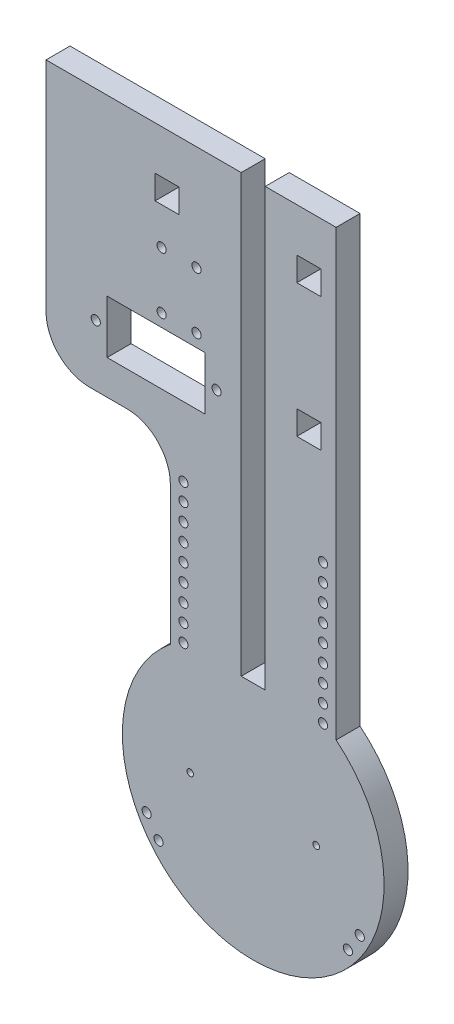
SolidWorks part; units mm, degrees
material "ﾁｰｸ材"
ref_plane "正面" through (0, 0, 0) normal (0, 0, 1) x (1, 0, 0)
ref_plane "平面" through (0, 0, 0) normal (0, 1, 0) x (1, 0, 0)
ref_plane "右側面" through (0, 0, 0) normal (1, 0, 0) x (0, 0, -1)
sketch "ｽｹｯﾁ1" plane through (0, 0, 0) normal (0, 0, 1) x (1, 0, 0)
  line L0 (19, 125) -> (-47.5, 125)
  line L2 (19, 125) -> (19, 23.2164)
  line L7 (-47.5, 65) -> (-47.5, 125)
  line L11 (-19, 65) -> (-19, 23.2164)
  line L12 (-19, 65) -> (-47.5, 65)
  arc A0 (-19, 23.2164) -> (19, 23.2164) centre (0, 0) ccw
  point P1 (-19, 85)
  dimension "D1" = 60
  dimension "D2" = 125
  dimension "D3" = 19
  dimension "D4" = 60
  dimension "D5" = 47.5
extrude "ﾎﾞｽ - 押し出し1" add sketch "ｽｹｯﾁ1" along normal blind 5.5
sketch "ｽｹｯﾁ3" plane through (0, 0, 5.5) normal (0, 0, 1) x (1, 0, 0)
  line L0 (0, 0) -> (0, 22.4882) construction
sketch "ｽｹｯﾁ5" plane through (0, 0, 5.5) normal (0, 0, 1) x (1, 0, 0)
  circle A0 centre (14.45, 0) radius 0.75
  circle A1 centre (-14.45, 0) radius 0.75
  dimension "D1" = 14.45
  dimension "D2" = 1.5
  dimension "D3" = 14.45
extrude "ｶｯﾄ - 押し出し3" cut sketch "ｽｹｯﾁ5" against normal through all
sketch "ｽｹｯﾁ6" plane through (0, 0, 5.5) normal (0, 0, 1) x (1, 0, 0)
  line L0 (0, 0) -> (-25.1601, -16.3392) construction
  line L1 (0, 0) -> (0, 22.4882) construction
  line L2 (-21.7018, -17.0742) -> (-24.425, -12.8809) construction
  line L3 (0, 0) -> (0, -5.9449) construction
  arc A0 (-19, 23.2164) -> (19, 23.2164) centre (0, 0) ccw construction
  circle A1 centre (-24.425, -12.8809) radius 1.05
  circle A2 centre (-21.7018, -17.0742) radius 1.05
  circle A3 centre (24.425, -12.8809) radius 1.05
  circle A4 centre (21.7018, -17.0742) radius 1.05
  point P12 (-23.0634, -14.9776)
  dimension "D2" = 5
  dimension "D3" = 2.1
  dimension "D4" = 2.1
  dimension "D1" = 123
  dimension "D5" = 27.5
extrude "ｶｯﾄ - 押し出し4" cut sketch "ｽｹｯﾁ6" against normal through all
sketch "ｽｹｯﾁ8" plane through (0, 0, 5.5) normal (0, 0, 1) x (1, 0, 0)
  line L0 (0, 0) -> (0, 22.4882) construction
  line L1 (15.5, 109.5) -> (10, 109.5)
  line L2 (15.5, 109.5) -> (15.5, 115)
  line L3 (15.5, 115) -> (10, 115)
  line L4 (10, 109.5) -> (10, 115)
  line L5 (-22.5, 115) -> (-17, 115)
  line L6 (-22.5, 115) -> (-22.5, 109.5)
  line L7 (-22.5, 109.5) -> (-17, 109.5)
  line L8 (-17, 115) -> (-17, 109.5)
  line L9 (19, 125) -> (-47.5, 125) construction
  line L10 (15.5, 79) -> (10, 79)
  line L11 (15.5, 79) -> (15.5, 84.5)
  line L12 (15.5, 84.5) -> (10, 84.5)
  line L13 (10, 79) -> (10, 84.5)
  point P10 (-17, 112.25)
  dimension "D1" = 5.5
  dimension "D2" = 10
  dimension "D3" = 17
  dimension "D4" = 10
  dimension "D5" = 25
extrude "ｶｯﾄ - 押し出し6" cut sketch "ｽｹｯﾁ8" against normal through all
sketch "ｽｹｯﾁ9" plane through (0, 0, 5.5) normal (0, 0, 1) x (1, 0, 0)
  line L0 (0, 0) -> (0, 22.4882) construction
  line L1 (0, 0) -> (0, 13.9203) construction
  circle A0 centre (16, 25) radius 1.05
  circle A1 centre (16, 29) radius 1.05
  circle A2 centre (16, 33) radius 1.05
  circle A3 centre (16, 37) radius 1.05
  circle A4 centre (16, 41) radius 1.05
  circle A5 centre (16, 45) radius 1.05
  circle A6 centre (16, 49) radius 1.05
  circle A7 centre (16, 53) radius 1.05
  circle A8 centre (16, 57) radius 1.05
  circle A9 centre (-16, 57) radius 1.05
  circle A10 centre (-16, 53) radius 1.05
  circle A11 centre (-16, 49) radius 1.05
  circle A12 centre (-16, 45) radius 1.05
  circle A13 centre (-16, 41) radius 1.05
  circle A14 centre (-16, 37) radius 1.05
  circle A15 centre (-16, 33) radius 1.05
  circle A16 centre (-16, 29) radius 1.05
  circle A17 centre (-16, 25) radius 1.05
  dimension "D1" = 2.1
  dimension "D2" = 16
  dimension "D4" = 25
  dimension "D3" = 9
extrude "ｶｯﾄ - 押し出し7" cut sketch "ｽｹｯﾁ9" against normal through all
sketch "ｽｹｯﾁ10" plane through (0, 0, 5.5) normal (0, 0, 1) x (1, 0, 0)
  line L0 (19, 125) -> (-47.5, 125) construction
  line L1 (2.75, 25) -> (-2.75, 25)
  line L2 (2.75, 25) -> (2.75, 125)
  line L3 (2.75, 125) -> (-2.75, 125)
  line L4 (-2.75, 25) -> (-2.75, 125)
  line L5 (2.75, 25) -> (-2.75, 125) construction
  line L6 (2.75, 125) -> (-2.75, 25) construction
  point P0 (0, 75)
  dimension "D1" = 5.5
  dimension "D2" = 25
extrude "ｶｯﾄ - 押し出し8" cut sketch "ｽｹｯﾁ10" against normal through all
sketch "ｽｹｯﾁ11" plane through (0, 0, 5.5) normal (0, 0, 1) x (1, 0, 0)
  line L0 (-2.75, 125) -> (-47.5, 125) construction
  line L1 (0, 0) -> (0, 22.4882) construction
  circle A0 centre (-13, 101) radius 1.05
  circle A1 centre (-21, 101) radius 1.05
  circle A2 centre (-13, 88) radius 1.05
  circle A3 centre (-21, 88) radius 1.05
  point P8 (-20.2729, 103.7087)
  dimension "D1" = 2.1
  dimension "D2" = 24
  dimension "D3" = 8
  dimension "D4" = 13
  dimension "D5" = 13
extrude "ｶｯﾄ - 押し出し9" cut sketch "ｽｹｯﾁ11" against normal through all
sketch "ｽｹｯﾁ12" plane through (0, 0, 5.5) normal (0, 0, 1) x (1, 0, 0)
  line L1 (-11, 72.9) -> (-33.5, 72.9)
  line L2 (-11, 72.9) -> (-11, 85.1)
  line L3 (-11, 85.1) -> (-33.5, 85.1)
  line L4 (-33.5, 72.9) -> (-33.5, 85.1)
  line L5 (-11, 72.9) -> (-33.5, 85.1) construction
  line L6 (-11, 85.1) -> (-33.5, 72.9) construction
  line L7 (0, 0) -> (0, 22.4882) construction
  line L8 (-2.75, 125) -> (-47.5, 125) construction
  circle A0 centre (-36.1, 79) radius 1.05
  circle A1 centre (-8.4, 79) radius 1.05
  point P0 (-22.25, 79)
  dimension "D5" = 2.1
  dimension "D1" = 12.2
  dimension "D2" = 22.5
  dimension "D3" = 11
  dimension "D4" = 46
  dimension "D6" = 2.6
  dimension "D7" = 2.6
extrude "ｶｯﾄ - 押し出し10" cut sketch "ｽｹｯﾁ12" against normal blind 10
fillet "ﾌｨﾚｯﾄ1" radius 10 2 edges at (-47.5, 65, 2.75) (-19, 65, 2.75)
